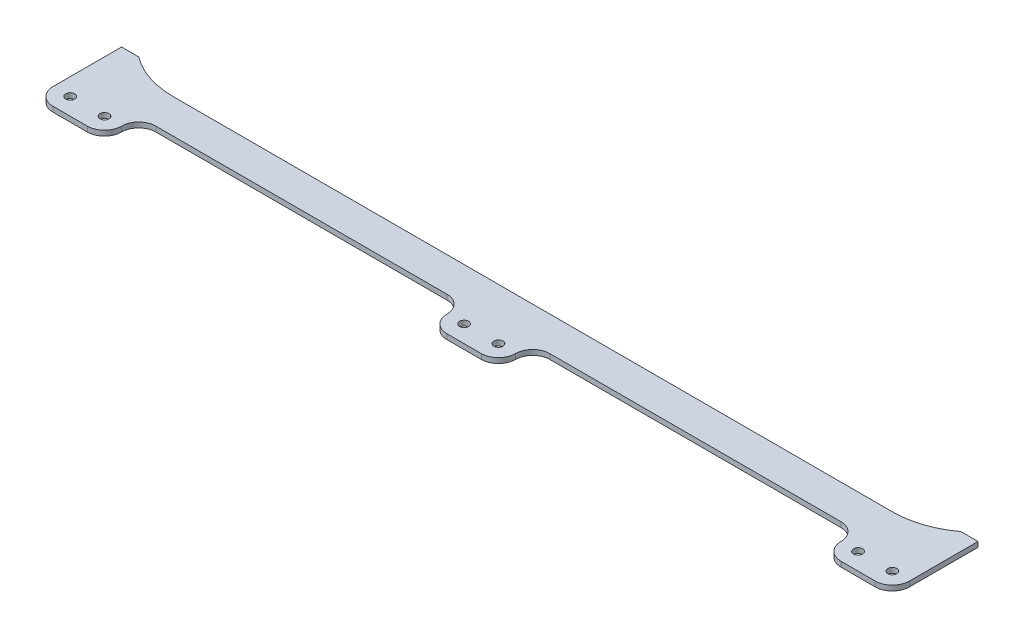
SolidWorks part; units mm, degrees
material "Сосна"
ref_plane "Спереди" through (0, 0, 0) normal (0, 0, 1) x (1, 0, 0)
ref_plane "Сверху" through (0, 0, 0) normal (0, 1, 0) x (1, 0, 0)
ref_plane "Справа" through (0, 0, 0) normal (1, 0, 0) x (0, 0, -1)
sketch "Эскиз1" plane through (0, 0, 0) normal (0, 1, 0) x (1, 0, 0)
  line L0 (-210, 5) -> (210, 5)
  line L1 (-250, -15) -> (250, -15)
  line L2 (-250, -15) -> (-250, 15)
  line L3 (-250, 15) -> (250, 15)
  line L4 (250, -15) -> (250, 15)
  line L5 (-250, -15) -> (250, 15) construction
  line L6 (-250, 15) -> (250, -15) construction
  line L7 (0, 0) -> (0, -50000) construction
  arc A0 (210, 5) -> (240, 15) centre (210, 55) ccw
  arc A1 (-210, 5) -> (-240, 15) centre (-210, 55) cw
  point P0 (0, 0)
  point P15 (0, 0)
  point P17 (192.2004, 0)
  dimension "D1" = 500
  dimension "D2" = 20
  dimension "D3" = 10
  dimension "D4" = 30
  dimension "D5" = 10
extrude "Бобышка-Вытянуть1" add sketch "Эскиз1" along normal blind 3 contours L0 A1 L3 L2 L1 L4 A0 region at (0, 0, 4.4731)
sketch "Эскиз2" plane through (0, 3, 0) normal (0, 1, 0) x (1, 0, 0)
  line L1 (250, -15) -> (210, -15)
  line L2 (250, -15) -> (250, -35)
  line L3 (250, -35) -> (210, -35)
  line L4 (210, -15) -> (210, -35)
  line L5 (230, -35) -> (230, -15) construction
  line L6 (250, -25) -> (210, -25) construction
  point P4 (0, 0)
  point P5 (251.7594, -21.3406)
  point P64 (230, -25)
  dimension "D1" = 40
  dimension "D2" = 20
extrude "Бобышка-Вытянуть2" add sketch "Эскиз2" against normal blind 3 contours L3 L4 L1 L2
hole_wizard "Отверстие с зазором M51" positions "Эскиз3" profile "Эскиз4" hole size "M5" standard "ISO" end condition up to next
sketch "Эскиз3" plane through (0, 3, 0) normal (0, 1, 0) x (1, 0, 0)
  line L0 (250, -35) -> (210, -35) construction
  line L1 (210, -15) -> (210, -35) construction
  point P0 (220, -25)
  point P2 (240, -25)
  dimension "D1" = 20
  dimension "D2" = 10
  dimension "D3" = 10
sketch "Эскиз4" plane through (220, 3, 25) normal (1, 0, 0) x (0, 0, 1)
  line L0 (0, 0) -> (0, 3.001)
  line L1 (0, 3.001) -> (2.65, 3.001)
  line L2 (2.65, 3.001) -> (2.65, 0)
  line L5 (2.65, 0) -> (0, 0)
  line L11 (0, -6.35) -> (0, 107.95) construction
  dimension "Диаметр сквозного отверстия" = 5.3
  dimension "Глубина сквозного отверстия" = 3.001
pattern_linear "Линейный массив1" count 3 spacing 230 along (-1, 0, 0) of "Отверстие с зазором M51", "Бобышка-Вытянуть2"
fillet "Скругление1" radius 10 10 edges at (-250, 1.5, 35) (-210, 1.5, 35) (-210, 1.5, 15) (-20, 1.5, 15) (-20, 1.5, 35) (20, 1.5, 35) (20, 1.5, 15) (210, 1.5, 15) (250, 1.5, 35) (210, 1.5, 35)
